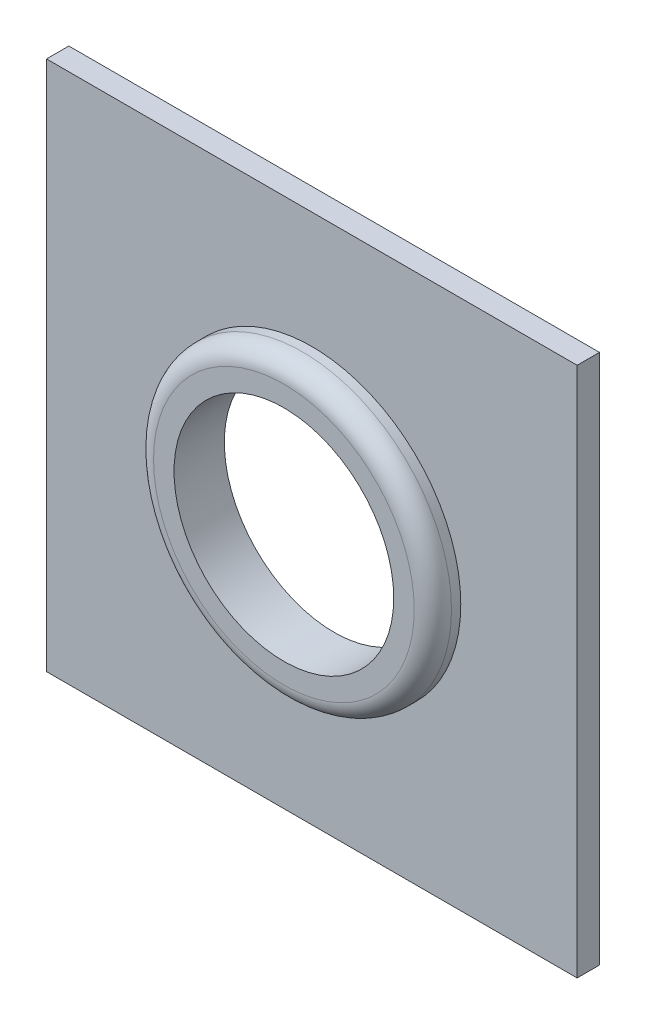
SolidWorks part; units mm, degrees
ref_plane "Front Plane" through (0, 0, 0) normal (0, 0, 1) x (1, 0, 0)
ref_plane "Top Plane" through (0, 0, 0) normal (0, 1, 0) x (1, 0, 0)
ref_plane "Right Plane" through (0, 0, 0) normal (1, 0, 0) x (0, 0, -1)
sketch "Sketch1" plane through (0, 0, 0) normal (0, 0, 1) x (1, 0, 0)
  line L1 (-14.25, -14.25) -> (14.25, -14.25)
  line L2 (-14.25, -14.25) -> (-14.25, 14.25)
  line L3 (-14.25, 14.25) -> (14.25, 14.25)
  line L4 (14.25, -14.25) -> (14.25, 14.25)
  line L5 (-14.25, -14.25) -> (14.25, 14.25) construction
  line L6 (-14.25, 14.25) -> (14.25, -14.25) construction
  circle A0 centre (0, 0) radius 5.9
  circle A1 centre (0, 0) radius 8
  dimension "D1" = 11.8
  dimension "D4" = 16
  dimension "D2" = 28.5
  dimension "D3" = 28.5
extrude "Boss-Extrude1" add sketch "Sketch1" along normal blind 1.2 contours A1 A0 | L1 L4 L3 L2 A1 region at (-13.8469, 0, 0) region at (-7.7737, 0, 0)
extrude "Boss-Extrude2" add sketch "Sketch1<3>" along normal blind 2.7 contours A1 A0 region at (-7.7737, 0, 0)
sketch "Sketch1<3>" plane through (0, 0, 0) normal (0, 0, 1) x (1, 0, 0) same geometry as "Sketch1"
fillet "Fillet1" radius 1 1 edges at (8, 0, 2.7)
